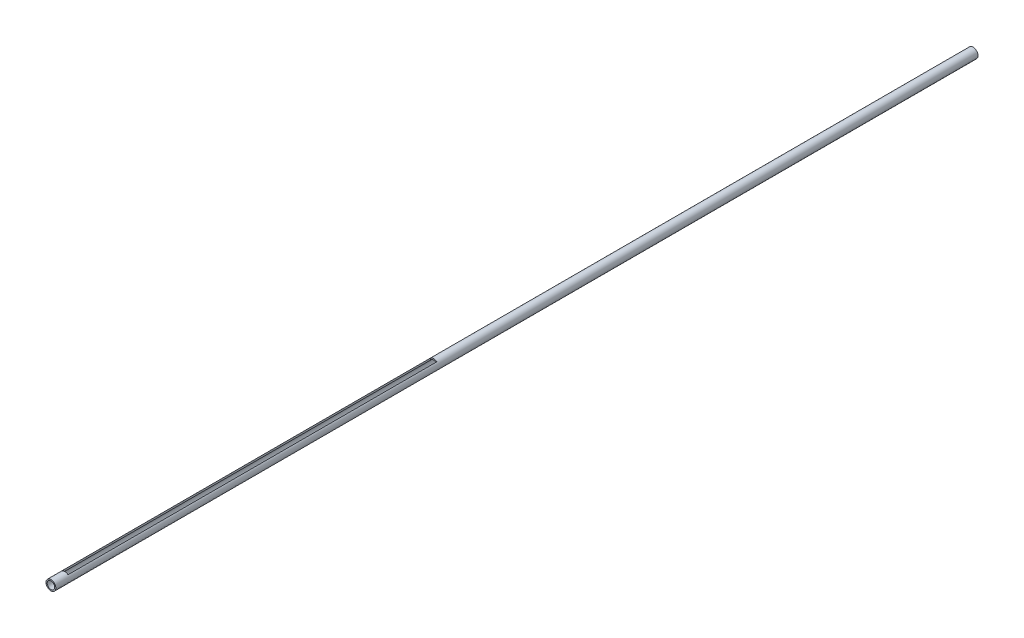
SolidWorks part; units mm, degrees
ref_plane "Front" through (0, 0, 0) normal (0, 0, 1) x (1, 0, 0)
ref_plane "Top" through (0, 0, 0) normal (0, 1, 0) x (1, 0, 0)
ref_plane "Right" through (0, 0, 0) normal (1, 0, 0) x (0, 0, -1)
sketch "Sketch1" plane through (0, 0, 0) normal (0, 0, 1) x (1, 0, 0)
  circle A0 centre (0, 0) radius 0.405
  circle A1 centre (0, 0) radius 0.535
  dimension "D1" = 0.81
  dimension "D2" = 1.07
extrude "Boss-Extrude1" add sketch "Sketch1" along normal blind 100
sketch "Sketch2" plane through (0, 0, 0) normal (0, 1, 0) x (1, 0, 0)
  line L0 (0, 0) -> (0, 1.8522) construction
  line L1 (-0.535, -100) -> (0.535, -100) construction
  line L2 (-0.35, -98.5) -> (0.35, -98.5)
  line L3 (-0.35, -98.5) -> (-0.35, -58.5)
  line L4 (-0.35, -58.5) -> (0.35, -58.5)
  line L5 (0.35, -98.5) -> (0.35, -58.5)
  dimension "D1" = 1.5
  dimension "D2" = 40
  dimension "D3" = 0.7
extrude "Cut-Extrude1" cut sketch "Sketch2" along normal through all
ref_axis "Axis-Tube19" through (0, 0, 100) along (0, 0, -1)
